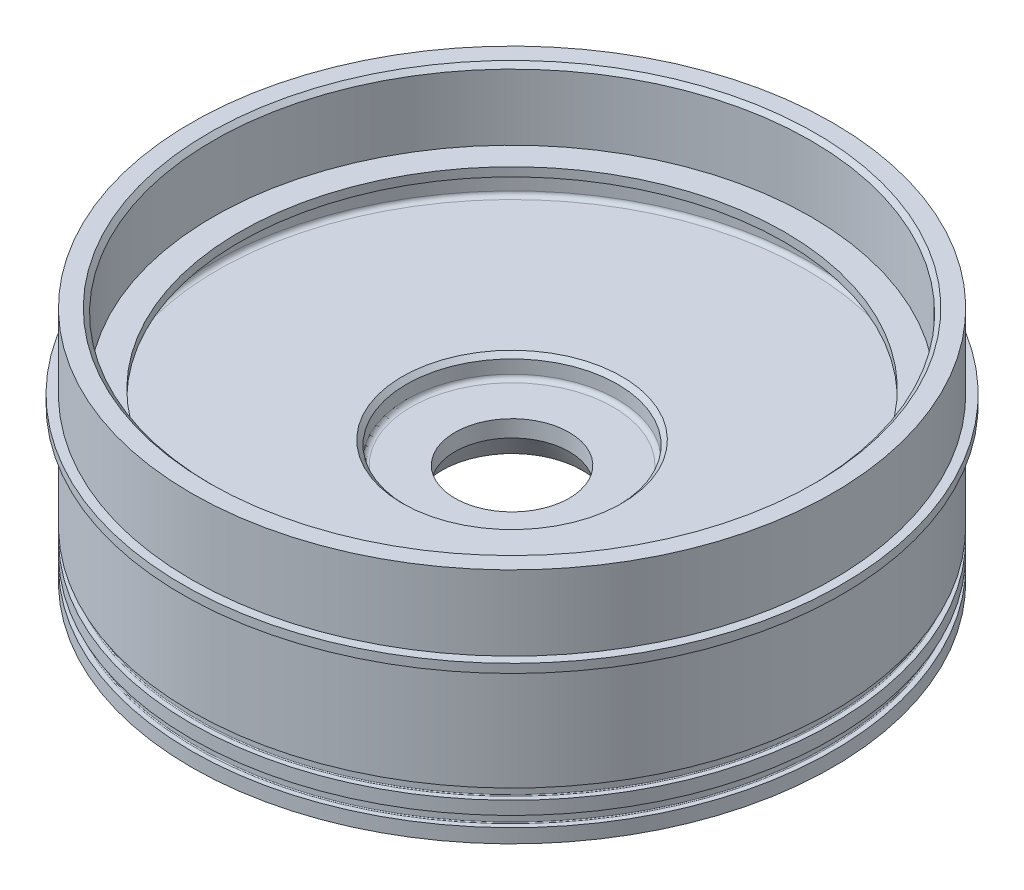
SolidWorks part; units mm, degrees
material "6061-T6 (SS)"
ref_plane "Piano frontale" through (0, 0, 0) normal (0, 0, 1) x (1, 0, 0)
ref_plane "Piano superiore" through (0, 0, 0) normal (0, 1, 0) x (1, 0, 0)
ref_plane "Piano destro" through (0, 0, 0) normal (1, 0, 0) x (0, 0, -1)
sketch "Schizzo1" plane through (0, 0, 0) normal (0, 0, 1) x (1, 0, 0)
  line L0 (0, 0) -> (0, 25.5769) construction
  line L1 (-13, 0) -> (-73, 0)
  line L2 (-73, 0) -> (-73, 14)
  line L3 (-73, 14) -> (-24, 14)
  line L4 (-24, 14) -> (-24, 9)
  line L5 (-24, 9) -> (-13, 9)
  line L6 (-13, 9) -> (-13, 0)
  line L7 (-24, 14) -> (-13, 14)
  line L8 (-13, 14) -> (-13, 9)
  line L9 (-73, 14) -> (-73, 40)
  line L10 (-73, 40) -> (-68, 40)
  line L11 (-69, 0) -> (-69, -14)
  line L12 (-69, -14) -> (-73, -14)
  line L13 (-73, -14) -> (-73, 0)
  line L14 (-68, 14) -> (-68, 40)
  line L15 (-73, 23) -> (-75, 23)
  line L16 (-75, 23) -> (-75, 21)
  line L17 (-73, -14) -> (-73, 0)
  line L18 (-73, -3) -> (-71.7, -3)
  line L19 (-71.7, -3) -> (-71.7, -5.4)
  line L20 (-71.7, -5.4) -> (-73, -5.4)
  line L21 (-73, -8.4) -> (-71.7, -8.4)
  line L22 (-71.7, -8.4) -> (-71.7, -10.8)
  line L23 (-71.7, -10.8) -> (-73, -10.8)
  line L24 (-75, 21) -> (-73, 21)
  line L25 (-68, 24) -> (-62, 24)
  line L26 (-62, 24) -> (-62, 22)
  line L27 (-62, 22) -> (-68, 22)
  dimension "D1" = 5
  dimension "D2" = 146
  dimension "D3" = 26
  dimension "D4" = 48
  dimension "D5" = 14
  dimension "D6" = 4
  dimension "D7" = 2.4
  dimension "D8" = 1.3
  dimension "D9" = 3
  dimension "D10" = 3
  dimension "D11" = 14
  dimension "D12" = 26
  dimension "D13" = 136
  dimension "D14" = 2
  dimension "D15" = 150
  dimension "D16" = 35
  dimension "D17" = 2
  dimension "D18" = 124
  dimension "D19" = 16
revolve "Rivoluzione1" add sketch "Schizzo1" angle 360 about L0 region at (-44.7166, 6.6847, 0) region at (-70.8307, -7.0125, 0) region at (-18.5, 11.5, 0) region at (-70.5, 27, 0) region at (-74, 22, 0) region at (-65, 23, 0)
chamfer "Smusso1" distance 3 angle 60 1 edges at (0, 0, -13) first distance on face at (0, 0, -69)
chamfer "Smusso2" distance 1 angle 45 1 edges at (0, -14, -69)
fillet "Raccordo1" radius 1 2 edges at (0, 0, -69) (0, 14, -68)
chamfer "Smusso3" distance 1 angle 45 1 edges at (0, 40, -68)
fillet "Raccordo2" radius 0.2 4 edges at (0, -8.4, -71.7) (0, -10.8, -71.7) (0, -3, -71.7) (0, -5.4, -71.7)
sketch "Schizzo2" plane through (0, 0, 0) normal (0, 0, 1) x (1, 0, 0)
  line L0 (0, 0) -> (0, 58.1242) construction
  line L1 (0, 0) -> (-27.2443, 0) construction
  line L2 (-68, 0) -> (68, 0) construction
  line L3 (-13, 9) -> (-24, 9)
  line L4 (-24, 9) -> (-24, 14)
  line L5 (67, 14) -> (-67, 14) construction
  line L6 (-24, 14) -> (-13, 14)
  line L7 (13, 14) -> (-13, 14) construction
  line L8 (-13, 14) -> (-13, 9)
  line L9 (-13, 9) -> (-13, 0) construction
  dimension "D1" = 5
  dimension "D2" = 48
revolve "Taglia-Rivoluzione1" cut sketch "Schizzo2" angle 360 about L0
fillet "Raccordo3" radius 1 1 edges at (0, 9, -24)
chamfer "Smusso4" distance 1 angle 45 1 edges at (0, 14, -24)
